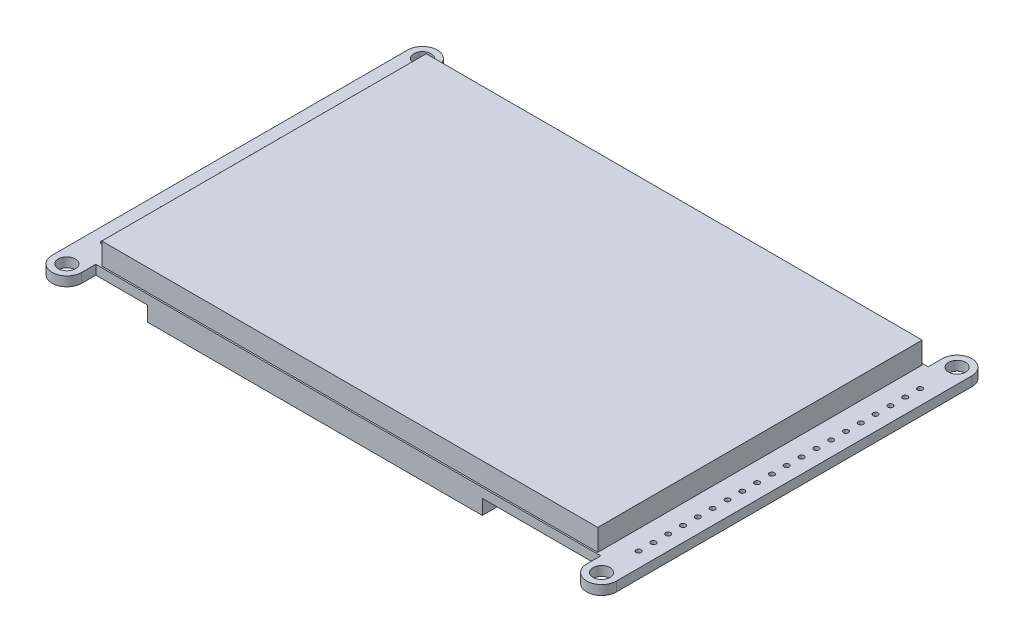
SolidWorks part; units mm, degrees
ref_plane "Front Plane" through (0, 0, 0) normal (0, 0, 1) x (1, 0, 0)
ref_plane "Top Plane" through (0, 0, 0) normal (0, 1, 0) x (1, 0, 0)
ref_plane "Right Plane" through (0, 0, 0) normal (1, 0, 0) x (0, 0, -1)
sketch "Sketch1" plane through (0, 0, 0) normal (0, 1, 0) x (1, 0, 0)
  line L0 (0, -28.067) -> (0, 28.067) construction
  line L1 (43.2943, 28.067) -> (-43.2943, 28.067)
  line L2 (43.2943, -28.067) -> (-43.2943, -28.067)
  line L3 (-43.2943, 28.067) -> (-43.2943, 30.48)
  line L4 (-48.3743, 30.48) -> (-48.3743, -30.48)
  line L5 (-43.2943, -30.48) -> (-43.2943, -28.067)
  line L6 (43.2943, -30.48) -> (43.2943, -28.067)
  line L7 (43.2943, 28.067) -> (43.2943, 30.48)
  line L8 (48.3743, 30.48) -> (48.3743, -30.48)
  line L9 (-45.8343, 24.13) -> (-45.8343, -24.13) construction
  line L10 (45.8343, 24.13) -> (45.8343, -24.13) construction
  line L12 (42.5196, -27.813) -> (-42.5196, -27.813)
  line L13 (42.5196, -27.813) -> (42.5196, 27.813)
  line L14 (42.5196, 27.813) -> (-42.5196, 27.813)
  line L15 (-42.5196, -27.813) -> (-42.5196, 27.813)
  line L16 (42.5196, -27.813) -> (-42.5196, 27.813) construction
  line L17 (42.5196, 27.813) -> (-42.5196, -27.813) construction
  circle A0 centre (-45.8343, 30.48) radius 1.4605
  arc A1 (-43.2943, 30.48) -> (-48.3743, 30.48) centre (-45.8343, 30.48) ccw
  arc A2 (-48.3743, -30.48) -> (-43.2943, -30.48) centre (-45.8343, -30.48) ccw
  circle A3 centre (-45.8343, -30.48) radius 1.4605
  circle A4 centre (45.8343, -30.48) radius 1.4605
  arc A5 (48.3743, -30.48) -> (43.2943, -30.48) centre (45.8343, -30.48) cw
  arc A6 (43.2943, 30.48) -> (48.3743, 30.48) centre (45.8343, 30.48) cw
  circle A7 centre (45.8343, 30.48) radius 1.4605
  circle A8 centre (-45.8343, 24.13) radius 0.4318
  circle A9 centre (-45.8343, 21.59) radius 0.4318
  circle A10 centre (-45.8343, 19.05) radius 0.4318
  circle A11 centre (-45.8343, 16.51) radius 0.4318
  circle A12 centre (-45.8343, 13.97) radius 0.4318
  circle A13 centre (-45.8343, 11.43) radius 0.4318
  circle A14 centre (-45.8343, 8.89) radius 0.4318
  circle A15 centre (-45.8343, 6.35) radius 0.4318
  circle A16 centre (-45.8343, 3.81) radius 0.4318
  circle A17 centre (-45.8343, 1.27) radius 0.4318
  circle A18 centre (-45.8343, -1.27) radius 0.4318
  circle A19 centre (-45.8343, -3.81) radius 0.4318
  circle A20 centre (-45.8343, -6.35) radius 0.4318
  circle A21 centre (-45.8343, -8.89) radius 0.4318
  circle A22 centre (-45.8343, -11.43) radius 0.4318
  circle A23 centre (-45.8343, -13.97) radius 0.4318
  circle A24 centre (-45.8343, -16.51) radius 0.4318
  circle A25 centre (-45.8343, -19.05) radius 0.4318
  circle A26 centre (-45.8343, -21.59) radius 0.4318
  circle A27 centre (-45.8343, -24.13) radius 0.4318
  circle A28 centre (45.8343, -24.13) radius 0.4318
  circle A29 centre (45.8343, -21.59) radius 0.4318
  circle A30 centre (45.8343, -19.05) radius 0.4318
  circle A31 centre (45.8343, -16.51) radius 0.4318
  circle A32 centre (45.8343, -13.97) radius 0.4318
  circle A33 centre (45.8343, -11.43) radius 0.4318
  circle A34 centre (45.8343, -8.89) radius 0.4318
  circle A35 centre (45.8343, -6.35) radius 0.4318
  circle A36 centre (45.8343, -3.81) radius 0.4318
  circle A37 centre (45.8343, -1.27) radius 0.4318
  circle A38 centre (45.8343, 1.27) radius 0.4318
  circle A39 centre (45.8343, 3.81) radius 0.4318
  circle A40 centre (45.8343, 6.35) radius 0.4318
  circle A41 centre (45.8343, 8.89) radius 0.4318
  circle A42 centre (45.8343, 11.43) radius 0.4318
  circle A43 centre (45.8343, 13.97) radius 0.4318
  circle A44 centre (45.8343, 16.51) radius 0.4318
  circle A45 centre (45.8343, 19.05) radius 0.4318
  circle A46 centre (45.8343, 21.59) radius 0.4318
  circle A47 centre (45.8343, 24.13) radius 0.4318
  point P3 (-45.8343, 0)
  point P4 (0, 0)
  point P8 (0, 28.067)
  point P11 (0, -28.067)
  point P19 (-45.8343, 33.02)
  point P22 (-45.8343, -33.02)
  point P23 (-48.3743, 0)
  point P35 (0, 0)
  dimension "D2" = 2.921
  dimension "D7" = 0.8636
  dimension "D1" = 66.04
  dimension "D3" = 5.08
  dimension "D4" = 56.134
  dimension "D5" = 96.7486
  dimension "D8" = 2.54
  dimension "D9" = 55.626
  dimension "D10" = 85.0392
  dimension "D6" = 20
extrude "Boss-Extrude1" add sketch "Sketch1" along normal blind 1.6256
extrude "Boss-Extrude2" add sketch "Sketch1<2>" along normal blind 5.334 contours L15 L12 L13 L14 region at (0, 0, 0)
sketch "Sketch1<2>" plane through (0, 0, 0) normal (0, 1, 0) x (1, 0, 0) same geometry as "Sketch1"
sketch "Sketch2" plane through (0, 0, 0) normal (0, -1, 0) x (1, 0, 0)
  line L0 (-48.3743, -30.48) -> (-48.3743, 30.48) construction
  line L1 (-34.4043, 28.067) -> (22.9743, 28.067)
  line L2 (-34.4043, 28.067) -> (-34.4043, -28.067)
  line L3 (-34.4043, -28.067) -> (22.9743, -28.067)
  line L4 (22.9743, 28.067) -> (22.9743, -28.067)
  line L5 (-34.4043, 28.067) -> (22.9743, -28.067) construction
  line L6 (-34.4043, -28.067) -> (22.9743, 28.067) construction
  line L7 (48.3743, 30.48) -> (48.3743, -30.48) construction
  line L8 (43.2943, -28.067) -> (-43.2943, -28.067) construction
  line L9 (-43.2943, 28.067) -> (43.2943, 28.067) construction
  point P0 (-5.715, 0)
  point P8 (0, 0)
  point P9 (0, 0)
  point P10 (0, 0)
  point P11 (0, 0)
  point P12 (0, 0)
  dimension "D1" = 13.97
  dimension "D2" = 25.4
extrude "Boss-Extrude3" add sketch "Sketch2" along normal blind 2.54 contours L4 L1 L2 L3 region at (-5.715, 0, 0)
